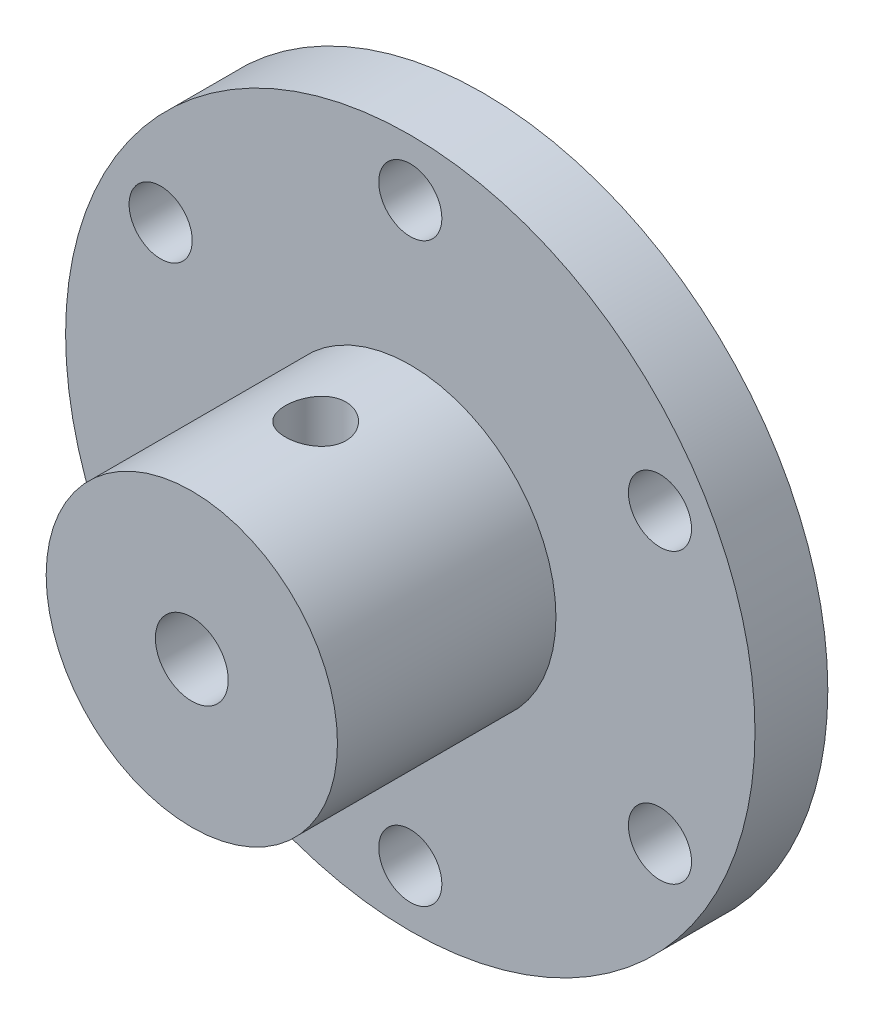
SolidWorks part; units mm, degrees
ref_plane "Front Plane" through (0, 0, 0) normal (0, 0, 1) x (1, 0, 0)
ref_plane "Top Plane" through (0, 0, 0) normal (0, 1, 0) x (1, 0, 0)
ref_plane "Right Plane" through (0, 0, 0) normal (1, 0, 0) x (0, 0, -1)
sketch "Sketch1" plane through (0, 0, 0) normal (0, 0, 1) x (1, 0, 0)
  circle A0 centre (0, 0) radius 28.4
  circle A1 centre (0, 23.75) radius 2.6
  circle A2 centre (0, 0) radius 23.75 construction
  circle A3 centre (20.5681, 11.875) radius 2.6
  circle A4 centre (20.5681, -11.875) radius 2.6
  circle A5 centre (0, -23.75) radius 2.6
  circle A6 centre (-20.5681, -11.875) radius 2.6
  circle A7 centre (-20.5681, 11.875) radius 2.6
  circle A8 centre (0, 0) radius 3
  point P19 (0, 0)
  dimension "D1" = 56.8
  dimension "D2" = 47.5
  dimension "D3" = 5.2
  dimension "D5" = 6
  dimension "D4" = 6
extrude "Boss-Extrude1" add sketch "Sketch1" along normal blind 6 contours A0 A8 A7 A6 A5 A4 A3 A1 | A8 region at (-27.5967, 0, 0) region at (0, 0, 0)
sketch "Sketch3" plane through (0, 0, 0) normal (0, 0, -1) x (-1, 0, 0)
  circle A0 centre (0, 0) radius 12
  dimension "D1" = 24
extrude "Boss-Extrude2" add sketch "Sketch3" against normal blind 24
extrude "Cut-Extrude1" cut sketch "Sketch1<3>" along normal up to surface (24 mm away) contours A8 region at (0, 0, 0) up to face at (-12, 0, 24)
sketch "Sketch1<3>" plane through (0, 0, 0) normal (0, 0, 1) x (1, 0, 0) same geometry as "Sketch1"
sketch "Sketch4" plane through (0, 0, 0) normal (0, 1, 0) x (1, 0, 0)
  line L0 (-12, -24) -> (12, -24) construction
  circle A0 centre (0, -13.8) radius 2.5
  dimension "D2" = 5
  dimension "D1" = 10.2
extrude "Cut-Extrude2" cut sketch "Sketch4" along normal up to surface (12 mm away) up to face at (12, 0, 6)
ref_axis "Axis1" through (0, 26.4267, 13.8) along (0, -1, 0)
